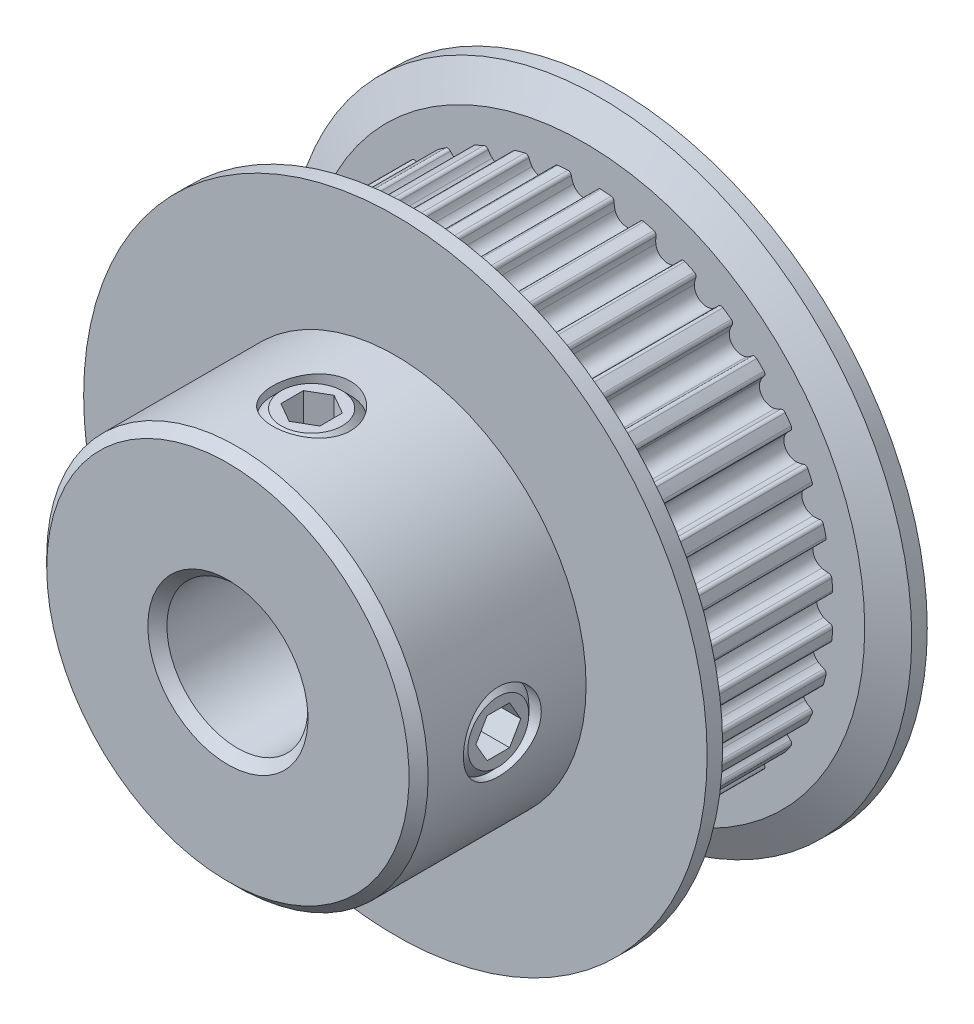
SolidWorks part; units mm, degrees
ref_plane "Front Plane" through (0, 0, 0) normal (0, 0, 1) x (1, 0, 0)
ref_plane "Top Plane" through (0, 0, 0) normal (0, 1, 0) x (1, 0, 0)
ref_plane "Right Plane" through (0, 0, 0) normal (1, 0, 0) x (0, 0, -1)
sketch "Sketch1" plane through (0, 0, 0) normal (0, 0, 1) x (1, 0, 0)
  line L1 (-1.8459, 10.4515) -> (1.8459, 10.4515) construction
  line L4 (0, 0) -> (0, 10.4515) construction
  line L5 (0, 10.4515) -> (0, 14.6042) construction
  line L6 (0, 11.4555) -> (1.9924, 11.2809) construction
  line L7 (1.9924, 11.2809) -> (2.8218, 11.1344) construction
  line L8 (1.9924, 11.2809) -> (1.8459, 10.4515) construction
  line L9 (-1.9924, 11.2809) -> (-1.8459, 10.4515) construction
  line L10 (-1.9482, 11.0308) -> (-2.4785, 14.0335)
  line L11 (-2.4785, 14.0335) -> (2.4785, 14.0335)
  line L12 (2.4785, 14.0335) -> (1.9482, 11.0308)
  circle A0 centre (0, 0) radius 11.4555 construction
  circle A1 centre (0, 0) radius 14.0335 construction
  circle A2 centre (0, 0) radius 11.2015 construction
  arc A3 (-0.4989, 10.7633) -> (0.4989, 10.7633) centre (0, 11.0065) ccw
  arc A4 (-0.4989, 10.7633) -> (-0.5884, 11.0497) centre (0.4, 11.2015) cw
  arc A5 (-1.9482, 11.0308) -> (-0.7467, 11.1766) centre (0, 0) cw
  arc A6 (-0.5884, 11.0497) -> (-0.7467, 11.1766) centre (-0.7367, 11.0269) ccw
  arc A7 (1.9482, 11.0308) -> (0.7467, 11.1766) centre (0, 0) ccw
  arc A8 (0.5884, 11.0497) -> (0.7467, 11.1766) centre (0.7367, 11.0269) cw
  arc A9 (0.4989, 10.7633) -> (0.5884, 11.0497) centre (-0.4, 11.2015) ccw
  point P6 (0, 20.9083)
  point P11 (0, 11.4555)
  point P13 (0, 14.0335)
  point P14 (0, 11.2015)
  dimension "D1" = 6.3042
  dimension "D2" = 3.1487
sketch "Sketch2" plane through (0, 0, 0) normal (1, 0, 0) x (0, 0, -1)
  line L0 (-8.7249, 3.175) -> (8.7249, 3.175)
  line L1 (-8.7249, 3.175) -> (-8.7249, 8.585)
  line L2 (-8.7249, 8.585) -> (-1.1851, 8.585)
  line L3 (-1.1851, 8.585) -> (-1.1851, 14.0335)
  line L4 (-1.1851, 14.0335) -> (0.2149, 14.0335) construction
  line L5 (0.2149, 14.0335) -> (0.2149, 11.2015) construction
  line L6 (0.2149, 11.2015) -> (7.3249, 11.2015)
  line L7 (7.3249, 11.2015) -> (7.3249, 14.0335) construction
  line L8 (7.3249, 14.0335) -> (8.7249, 14.0335) construction
  line L9 (8.7249, 14.0335) -> (8.7249, 3.175)
  line L10 (-8.7249, 0) -> (8.7249, 0) construction
  line L11 (8.0249, 14.0335) -> (7.3249, 12.6175)
  line L12 (0.2149, 12.6175) -> (-0.4851, 14.0335)
  line L13 (-1.1851, 14.0335) -> (-0.4851, 14.0335)
  line L14 (0.2149, 12.6175) -> (0.2149, 11.2015)
  line L15 (7.3249, 11.2015) -> (7.3249, 12.6175)
  line L16 (8.0249, 14.0335) -> (8.7249, 14.0335)
  arc A0 (0.2149, 12.6175) -> (-0.4851, 14.0335) centre (-1.5673, 12.6175) ccw construction
  arc A1 (7.3249, 12.6175) -> (8.0249, 14.0335) centre (9.1071, 12.6175) cw construction
  point P12 (0.2149, 12.6175)
  point P14 (-0.4851, 14.0335)
  point P20 (7.3249, 12.6175)
  point P21 (8.0249, 14.0335)
  point P25 (7.3249, 0)
  point P26 (0.2149, 0)
revolve "Revolve1" add sketch "Sketch2" angle 360 mid plane about L10
sketch "Sketch3" plane through (0, 0, 0) normal (0, 0, 1) x (1, 0, 0)
  line L6 (2.4785, 14.0335) -> (-2.4785, 14.0335)
  line L7 (1.9482, 11.0308) -> (2.4785, 14.0335)
  line L8 (-2.4785, 14.0335) -> (-1.9482, 11.0308)
  line L9 (2.4785, 14.0335) -> (-2.4785, 14.0335)
  line L10 (1.9482, 11.0308) -> (2.4785, 14.0335)
  line L11 (-2.4785, 14.0335) -> (-1.9482, 11.0308)
  arc A8 (1.9482, 11.0308) -> (0.7467, 11.1766) centre (0, 0) ccw
  arc A9 (0.7467, 11.1766) -> (0.5884, 11.0497) centre (0.7367, 11.0269) ccw
  arc A10 (0.4989, 10.7633) -> (0.5884, 11.0497) centre (-0.4, 11.2015) ccw
  arc A11 (-0.4989, 10.7633) -> (0.4989, 10.7633) centre (0, 11.0065) ccw
  arc A12 (-0.5884, 11.0497) -> (-0.4989, 10.7633) centre (0.4, 11.2015) ccw
  arc A13 (-0.5884, 11.0497) -> (-0.7467, 11.1766) centre (-0.7367, 11.0269) ccw
  arc A14 (-0.7467, 11.1766) -> (-1.9482, 11.0308) centre (0, 0) ccw
  arc A15 (1.9482, 11.0308) -> (0.7467, 11.1766) centre (0, 0) ccw
  arc A16 (0.7467, 11.1766) -> (0.5884, 11.0497) centre (0.7367, 11.0269) ccw
  arc A17 (0.4989, 10.7633) -> (0.5884, 11.0497) centre (-0.4, 11.2015) ccw
  arc A18 (-0.4989, 10.7633) -> (0.4989, 10.7633) centre (0, 11.0065) ccw
  arc A19 (-0.5884, 11.0497) -> (-0.4989, 10.7633) centre (0.4, 11.2015) ccw
  arc A20 (-0.5884, 11.0497) -> (-0.7467, 11.1766) centre (-0.7367, 11.0269) ccw
  arc A21 (-0.7467, 11.1766) -> (-1.9482, 11.0308) centre (0, 0) ccw
  dimension "D1" = 0
extrude "Cut-Extrude1" cut sketch "Sketch3" against normal up to vertex (7.3249 mm away) from vertex up to point (0, 11.2015, -7.3249) starting at point (0, 11.2015, -0.2149)
pattern_circular "CirPattern1" count 36 over 360 about axis through (0, 0, 8.7249) along (0, 0, 1) of "Cut-Extrude1"
sketch "Sketch4" plane through (0, 0, 0) normal (1, 0, 0) x (0, -1, 0)
  line L0 (0, -1.1851) -> (0, -8.7249) construction
  line L1 (-8.585, -1.1851) -> (8.585, -1.1851) construction
  line L2 (-8.585, -8.7249) -> (8.585, -8.7249) construction
  circle A0 centre (0, -4.955) radius 1.7526
extrude "Cut-Extrude2" cut sketch "Sketch4" along normal through all
ref_plane "Plane1" through (0, 0, 4.955) normal (0, 0, 1) x (1, 0, 0)
sketch "Sketch5" plane through (0, 0, 4.955) normal (0, 0, 1) x (1, 0, 0)
  line L0 (0, 0.1664) -> (0, 8.585) construction
  line L1 (3.175, -1.3716) -> (3.175, 0)
  line L2 (3.556, -1.7526) -> (8.0232, -1.7526)
  line L3 (3.175, 0) -> (8.585, 0) construction
  line L4 (3.175, 0) -> (8.4042, 0)
  line L5 (8.4042, 0) -> (8.4042, -1.3716)
  line L6 (3.556, -1.7526) -> (3.175, -1.3716)
  line L7 (8.4042, -1.3716) -> (8.0232, -1.7526)
  circle A0 centre (0, 0) radius 8.585 construction
  circle A1 centre (0, 0) radius 3.175 construction
  point P2 (3.175, -1.7526)
  point P11 (8.4042, -1.7526)
revolve "Revolve2" add sketch "Sketch5" angle 360 mid plane about L4
sketch "Sketch6" plane through (8.4042, 5.3841, 0) normal (-1, 0, 0) x (0, -1, 0)
  line L1 (5.3841, 5.9669) -> (4.5078, 5.4609)
  line L2 (4.5078, 5.4609) -> (4.5078, 4.4491)
  line L3 (4.5078, 4.4491) -> (5.3841, 3.9431)
  line L4 (5.3841, 3.9431) -> (6.2604, 4.4491)
  line L5 (6.2604, 4.4491) -> (6.2604, 5.4609)
  line L6 (6.2604, 5.4609) -> (5.3841, 5.9669)
  circle A0 centre (5.3841, 4.955) radius 0.8763 construction
  dimension "D1" = 1.7526
extrude "Cut-Extrude3" cut sketch "Sketch6" along normal blind 1.3144
pattern_circular "CirPattern2" count 2 over 90 about axis through (0, 0, 8.7249) along (0, 0, 1) of "Cut-Extrude2", "Revolve2", "Cut-Extrude3"
chamfer "Chamfer1" distance 0.4293 angle 45 2 edges at (3.175, 0, 8.7249) (8.585, 0, 8.7249)
ref_axis "Center Axis 1" through (0, 0, -8.7249) along (0, 0, 1)
ref_plane "Contact Plane 1" through (0, 0, 8.7249) normal (0, 0, 1) x (1, 0, 0)
ref_plane "Contact Plane 2" through (0, 0, -8.7249) normal (0, 0, -1) x (-1, 0, 0)
equation "\"D2@Sketch1\" = \"D1@Sketch1\"/2"
equation "\"D1@Sketch6\" = \"Set Screw@Sketch4\" / 2"
equation "\"D1@Cut-Extrude3\" = \"D1@Sketch6\"*.75"
equation "\"D1@Chamfer1\"=\"Hub Dia@Sketch2\"*.025"
